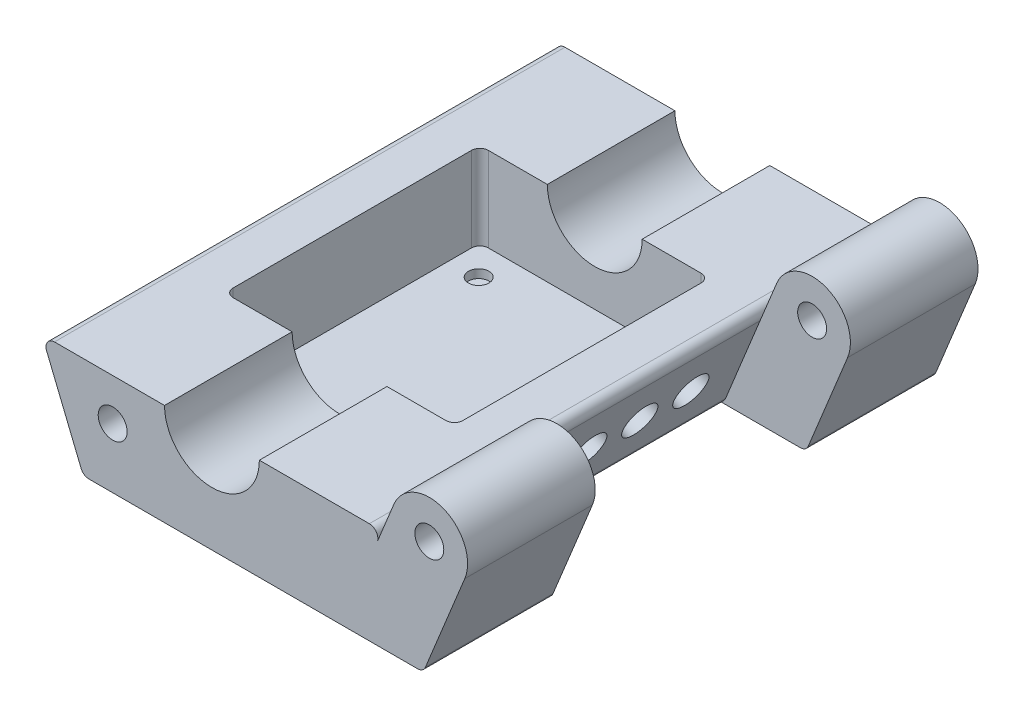
SolidWorks part; units mm, degrees
ref_plane "Front Plane" through (0, 0, 0) normal (0, 0, 1) x (1, 0, 0)
ref_plane "Top Plane" through (0, 0, 0) normal (0, 1, 0) x (1, 0, 0)
ref_plane "Right Plane" through (0, 0, 0) normal (1, 0, 0) x (0, 0, -1)
sketch "Sketch5" plane through (0, 0, 0) normal (0, 0, 1) x (1, 0, 0)
  line L0 (0, 25.6579) -> (0, -11.7437) construction
  line L1 (-26.0638, 0) -> (29.5961, 0) construction
  line L2 (-5.575, 9.9357) -> (5.575, 9.9357) construction
  line L4 (-5.575, 9.9357) -> (-18.5056, 9.9357)
  line L5 (-19.4314, 8.5579) -> (-15.3763, -1.3779)
  line L6 (-14.4505, -2) -> (14.4505, -2)
  line L7 (15.3763, -1.3779) -> (19.4314, 8.5579)
  line L8 (18.5056, 9.9357) -> (5.575, 9.9357)
  line L9 (0, 9.9357) -> (0, 4.3607) construction
  arc A3 (-5.575, 9.9357) -> (5.575, 9.9357) centre (0, 9.9357) ccw
  arc A4 (19.4314, 8.5579) -> (18.5056, 9.9357) centre (18.5056, 8.9357) ccw
  arc A5 (14.4505, -2) -> (15.3763, -1.3779) centre (14.4505, -1) ccw
  arc A6 (-15.3763, -1.3779) -> (-14.4505, -2) centre (-14.4505, -1) ccw
  arc A7 (-18.5056, 9.9357) -> (-19.4314, 8.5579) centre (-18.5056, 8.9357) ccw
  point P15 (19.9938, 9.9357)
  point P23 (-19.9938, 9.9357)
  dimension "D1" = 2
  dimension "D2" = 5.575
  dimension "D4" = 1
  dimension "D3" = 11.15
sketch "Sketch7" plane through (0, 0, 0) normal (0, 0, 1) x (1, 0, 0)
  line L0 (0, 48.7541) -> (0, -40.4703) construction
  line L1 (-34.5809, 0) -> (43.1676, 0) construction
sketch "Sketch8" plane through (0, 0, 0) normal (0, 1, 0) x (1, 0, 0)
  line L0 (0, 24.2687) -> (0, -29.4807) construction
  line L1 (-38.4914, 0) -> (52.0489, 0) construction
  line L3 (-12.5, 15) -> (12.5, 15)
  line L4 (-13.5, 14) -> (-13.5, -14)
  line L5 (-12.5, -15) -> (12.5, -15)
  line L6 (13.5, 14) -> (13.5, -14)
  arc A0 (12.5, 15) -> (13.5, 14) centre (12.5, 14) cw
  arc A1 (12.5, -15) -> (13.5, -14) centre (12.5, -14) ccw
  arc A2 (-13.5, -14) -> (-12.5, -15) centre (-12.5, -14) ccw
  arc A3 (-12.5, 15) -> (-13.5, 14) centre (-12.5, 14) ccw
  dimension "D1" = 1
  dimension "D2" = 27
  dimension "D3" = 30
extrude "Boss-Extrude3" add sketch "Sketch5" along normal blind 30 and the other way blind 30 contours L4 A7 L5 A6 L6 A5 L7 A4 L8 A3
extrude "Cut-Extrude1" cut sketch "Sketch8" along normal up to surface (9.9357 mm away) up to face at (12.0403, 9.9357, 0)
sketch "Sketch1" plane through (0, 0, 0) normal (0, 1, 0) x (1, 0, 0)
  line L0 (0, 33.0132) -> (0, -40.1974) construction
  circle A4 centre (-10.105, 11.46) radius 1.205
  circle A5 centre (-10.105, -11.46) radius 1.205
  circle A6 centre (10.0266, -11.46) radius 1.205
  circle A7 centre (10.105, 11.46) radius 1.205
  point P33 (-11.31, 11.46)
  point P34 (11.31, 11.46)
  point P35 (-10.105, 12.665)
  point P36 (-10.105, -12.665)
  dimension "D6" = 2.41
  dimension "D5" = 22.62
extrude "Cut-Extrude2" cut sketch "Sketch1" against normal blind 1
sketch "Sketch9" plane through (13.6628, -5.5762, 0) normal (0.9259, -0.3779, 0) x (0, 0, -1)
  line L0 (0, 28.5621) -> (0, -16.6059) construction
  line L1 (0, 45.1393) -> (0, -37.4697) construction
  circle A1 centre (-9, 9.6184) radius 2
  circle A2 centre (-3, 9.6184) radius 2
  circle A3 centre (3, 9.6184) radius 2
  circle A4 centre (9, 9.6184) radius 2
  dimension "D1" = 6
  dimension "D2" = 3
  dimension "D3" = 9
extrude "Cut-Extrude3" cut sketch "Sketch9" against normal up to surface (4.9177 mm away) up to face at (13.5, 4.9679, 0)
sketch "Sketch20" plane through (0, 0, 0) normal (0, 0, 1) x (1, 0, 0)
  line L6 (0, 51.5275) -> (0, -45.7952) construction
  line L12 (19.4314, 8.5579) -> (15.3763, -1.3779)
  line L13 (21.3854, 13.3455) -> (19.4314, 8.5579)
  line L14 (25.097, -1.3779) -> (29.7181, 9.9446)
  line L15 (14.4505, -2) -> (24.1712, -2)
  arc A9 (15.3763, -1.3779) -> (14.4505, -2) centre (14.4505, -1) cw
  arc A10 (24.1712, -2) -> (25.097, -1.3779) centre (24.1712, -1) ccw
  circle A11 centre (25.5518, 11.645) radius 1.7
  arc A12 (21.3854, 13.3455) -> (29.7181, 9.9446) centre (25.5518, 11.645) cw
  dimension "D4" = 4.5
  dimension "D5" = 3.4
  dimension "D6" = 1
extrude "Boss-Extrude5" add sketch "Sketch20" along normal up to surface (-15 mm away) from surface up to face at (0, 5.6947, -15) starting at face at (0, 4.4739, -30)
extrude "Boss-Extrude6" add sketch "Sketch20<2>" against normal up to surface (-15 mm away) from surface up to face at (0, 5.6947, 15) starting at face at (0, 4.4739, 30)
sketch "Sketch20<2>" plane through (0, 0, 0) normal (0, 0, 1) x (1, 0, 0) same geometry as "Sketch20"
sketch "Sketch22" plane through (0, 0, 0) normal (0, 0, 1) x (1, 0, 0)
  line L0 (0, 26.5719) -> (0, -17.8662) construction
  line L1 (0, 48.7541) -> (0, -40.4703) construction
  circle A0 centre (-11.6678, 5.056) radius 1.7
extrude "Cut-Extrude6" cut sketch "Sketch22" against normal blind 1 and the other way blind 10 from surface starting at face at (6.0205, 6.0163, -30)
extrude "Cut-Extrude7" cut sketch "Sketch22<2>" along normal blind 10 and the other way blind 10 from surface starting at face at (6.0205, 6.0163, 30)
sketch "Sketch22<2>" plane through (0, 0, 0) normal (0, 0, 1) x (1, 0, 0) same geometry as "Sketch22"
